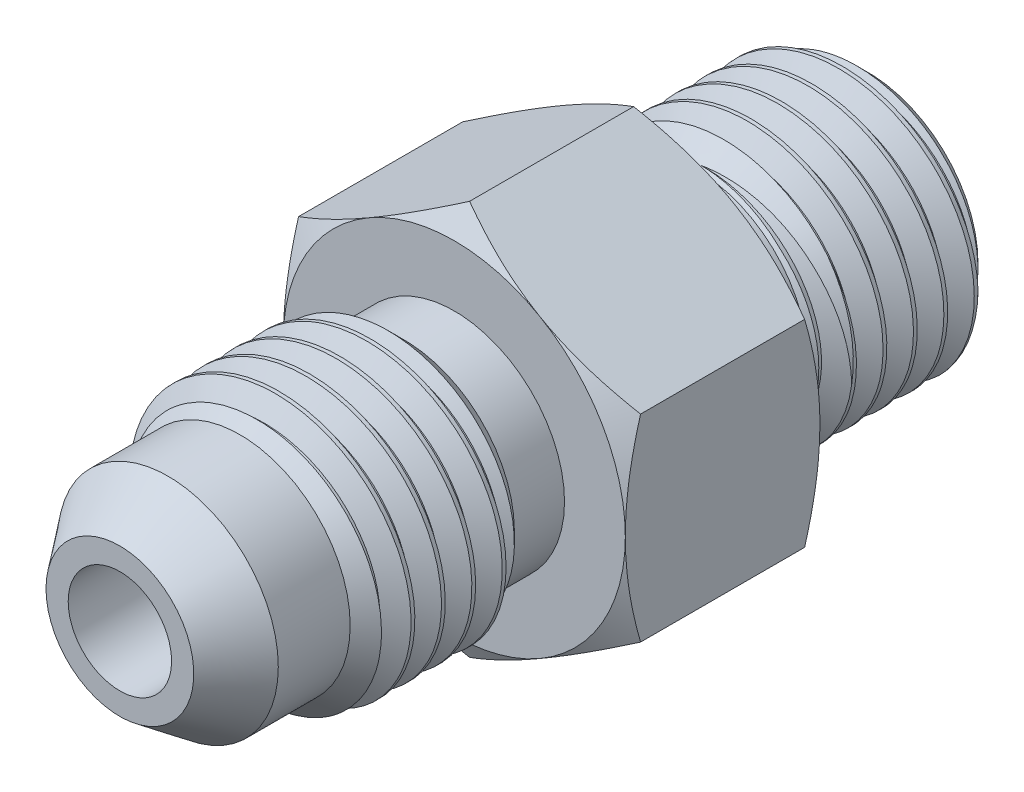
SolidWorks part; units mm, degrees
other "O-Ring" parameters "D8"=0.9525, "D1"=15.3309, "Thread Length 2"=7.112, "D2"=35.3119, "Thread Diameter 2"=6.35, "Minimum ID 2"=7.62, "Thread Pitch 2"=1.27, "Side Length 2"=9.144, "Length"=31.3538, "Side Length 1"=13.97, "Thread Length 1"=6.858, "Thread Diameter 1"=5.5562, "D3"=1.5238, "Thread 1 Offset"=0.9525, "Thread 2 Offset"=0.9525, "Thread Pitch 1"=1.27, "D4"=12.8, "Side Length Offset"=11.8745, "D5"=5.0165, "D6"=11.1125, "D7"=0.9525, "Side Length 1 Offset"=11.8745, "Face Diameter 1"=6.1722
ref_plane "Front Plane" through (0, 0, 0) normal (0, 0, 1) x (1, 0, 0)
ref_plane "Top Plane" through (0, 0, 0) normal (0, 1, 0) x (1, 0, 0)
ref_plane "Right Plane" through (0, 0, 0) normal (1, 0, 0) x (0, 0, -1)
sketch "Sketch1" plane through (0, 0, 0) normal (0, 0, 1) x (1, 0, 0)
  line L0 (0, -24.1967) -> (0, 24.1967) construction
  line L1 (0, 8.2489) -> (-7.1437, 4.1244) construction
  line L2 (-7.1437, 4.1244) -> (-7.1438, -4.1244) construction
  line L3 (-7.1438, -4.1244) -> (0, -8.2489) construction
  line L4 (0, -8.2489) -> (7.1438, -4.1244) construction
  line L5 (7.1438, -4.1244) -> (7.1438, 4.1244) construction
  line L6 (7.1438, 4.1244) -> (0, 8.2489) construction
  circle A0 centre (0, 0) radius 7.1438 construction
  circle A1 centre (0, 0) radius 2.159 construction
  point P1 (-2.159, 0)
  point P10 (-7.1437, 4.1244)
  point P11 (7.1438, 4.1244)
  point P13 (2.159, 0)
  point P14 (0, 2.159)
  point P15 (0, -2.159)
  point P16 (0, -7.1438)
  point P19 (-7.1438, -4.1244)
  point P20 (0, 8.2489)
  point P21 (0, -8.2489)
  point P22 (7.1438, -4.1244)
  point P23 (0, 7.1438)
  point P24 (7.1437, 0)
  point P25 (-7.1438, 0)
  dimension "Hex" = 14.2875
  dimension "Minimum ID 1" = 4.318
sketch "Sketch2" plane through (0, 0, 0) normal (1, 0, 0) x (0, 0, -1)
  line L0 (15.621, 0) -> (-15.621, 0) construction
  line L1 (8.509, 4.6037) -> (9.4615, 5.5562) construction
  line L2 (20.955, 0) -> (-20.955, 0) construction
  line L11 (-1.651, 7.1438) -> (6.477, 7.1438) construction
  line L12 (6.477, 7.1438) -> (6.477, 4.6037) construction
  line L13 (6.477, 4.6037) -> (8.509, 4.6037) construction
  line L21 (-15.621, 2.159) -> (-15.621, 4.6037) construction
  line L22 (8.509, 4.6037) -> (8.509, 5.5562) construction
  line L23 (8.509, 5.5562) -> (15.621, 5.5562) construction
  line L24 (15.621, 4.6037) -> (14.6685, 5.5562) construction
  line L25 (15.621, 5.5562) -> (15.621, 2.159) construction
  line L27 (-10.6045, 4.6037) -> (-10.6045, 5.5562) construction
  line L28 (-10.6045, 5.5562) -> (-3.7465, 5.5562) construction
  line L29 (-3.7465, 5.5562) -> (-3.7465, 4.6037) construction
  line L30 (-3.7465, 4.6037) -> (-1.651, 4.6037) construction
  line L31 (-1.651, 4.6037) -> (-1.651, 7.1438) construction
  line L32 (-10.6045, -5.5562) -> (-3.7465, -5.5562) construction
  line L33 (15.621, -5.5563) -> (8.509, -5.5562) construction
  line L34 (15.5416, 5.6937) -> (16.8116, 5.6937) construction
  line L35 (16.8116, 5.6937) -> (16.1766, 4.5939) construction
  line L36 (16.1766, 4.5939) -> (15.5416, 5.6937) construction
  line L37 (15.5813, 5.625) -> (16.7719, 5.625) construction
  line L38 (15.621, 5.5562) -> (16.7322, 5.5562) construction
  line L39 (16.0972, 4.7314) -> (16.256, 4.7314) construction
  line L40 (16.1766, 4.7314) -> (16.1766, 4.5939) construction
  line L41 (16.1766, 5.6937) -> (16.1766, 5.5562) construction
  line L42 (-11.7951, 5.6937) -> (-10.5251, 5.6937) construction
  line L43 (-10.5251, 5.6937) -> (-11.1601, 4.5939) construction
  line L44 (-11.1601, 4.5939) -> (-11.7951, 5.6937) construction
  line L45 (-11.7554, 5.625) -> (-10.5648, 5.625) construction
  line L46 (-11.7158, 5.5562) -> (-10.6045, 5.5562) construction
  line L47 (-11.2395, 4.7314) -> (-11.0808, 4.7314) construction
  line L48 (-11.1601, 4.7314) -> (-11.1601, 4.5939) construction
  line L49 (-11.1601, 5.5562) -> (-11.1601, 5.6937) construction
  line L53 (-15.621, 3.0861) -> (-13.607, 4.6037) construction
  line L54 (-1.651, 4.6037) -> (2.413, 4.6037) construction
  line L55 (6.477, 4.6037) -> (2.413, 4.6037) construction
  line L58 (-15.621, 2.159) -> (-1.651, 2.159) construction
  line L59 (-1.651, 2.159) -> (6.477, 2.159) construction
  line L60 (6.477, 2.159) -> (15.621, 2.159) construction
  line L61 (2.413, 2.159) -> (2.413, 7.1438) construction
  line L63 (-10.6045, 4.6037) -> (-9.652, 5.5562) construction
  line L64 (-15.621, 4.6037) -> (-10.6045, 4.6037) construction
  line L65 (-3.7465, 4.6037) -> (-4.699, 5.5562) construction
  circle A0 centre (6.9532, 5.08) radius 0.4763 construction
  point P4 (0, 0)
  point P10 (15.621, 4.6037)
  point P11 (-15.621, 2.159)
  point P16 (-10.6045, 5.5562)
  point P21 (-15.621, 4.6037)
  point P22 (-3.7465, 5.5562)
  point P24 (15.621, -5.5563)
  point P25 (-10.6045, 5.5562)
  point P26 (8.509, 4.6037)
  point P28 (15.621, 0)
  point P29 (13.716, -5.5563)
  point P31 (-1.651, 7.1438)
  point P34 (15.621, 5.5562)
  point P35 (-15.621, 0)
  point P38 (15.621, 2.159)
  point P52 (16.1766, 5.625)
  point P53 (16.256, 4.7314)
  point P54 (16.7322, 5.5562)
  point P55 (16.0972, 4.7314)
  point P56 (16.8116, 5.6937)
  point P57 (15.621, 5.5562)
  point P58 (15.5416, 5.6937)
  point P59 (-8.6995, -5.5562)
  point P66 (6.477, 7.1438)
  point P71 (-11.7158, 5.5562)
  point P72 (-11.7951, 5.6937)
  point P73 (-10.6045, 5.5562)
  point P74 (-10.5251, 5.6937)
  point P75 (-11.2395, 4.7314)
  point P76 (-11.0808, 4.7314)
  point P79 (-11.1601, 5.625)
  point P82 (-15.621, 3.0861)
  point P83 (-10.6045, -5.5562)
  point P84 (-13.607, 4.6037)
  dimension "D2" = 0.1588
  dimension "Length" = 31.242
  dimension "D1" = 1.905
  dimension "Thread 2 Offset" = 0.9525
  dimension "D3" = 0.1588
  dimension "D4" = 1.905
  dimension "Thread Diameter 1" = 11.1125
  dimension "Thread Diameter 2" = 11.1125
  dimension "D6" = 45
  dimension "D7" = 45
  dimension "Minimum ID 2" = 4.318
  dimension "D5" = 37
ref_plane "Plane1" through (0, 0, 10.6045) normal (0, 0, 1) x (1, 0, 0)
ref_plane "Plane2" through (0, 0, -15.621) normal (0, 0, 1) x (1, 0, 0)
ref_plane "Plane3" through (0, 0, 1.651) normal (0, 0, 1) x (1, 0, 0)
sketch "Sketch3" plane through (0, 0, 0) normal (1, 0, 0) x (0, 0, -1)
  line L0 (15.621, 0) -> (-15.621, 0) construction
  line L1 (-15.621, 2.159) -> (-15.621, 4.6037) construction
  line L2 (-15.621, 2.159) -> (-1.651, 2.159) construction
  line L3 (-1.651, 2.159) -> (6.477, 2.159) construction
  line L4 (6.477, 2.159) -> (15.621, 2.159) construction
  line L5 (15.621, 5.5562) -> (15.621, 2.159) construction
  line L6 (15.621, 4.6037) -> (14.6685, 5.5562) construction
  line L7 (8.509, 5.5562) -> (15.621, 5.5562) construction
  line L8 (8.509, 4.6037) -> (9.4615, 5.5562) construction
  line L10 (-3.7465, 4.6037) -> (-1.651, 4.6037)
  line L12 (-15.621, 4.6037) -> (-10.6045, 4.6037) construction
  line L14 (8.509, 4.6037) -> (6.477, 4.6037)
  line L15 (-10.6045, 5.5562) -> (-3.7465, 5.5562) construction
  line L16 (-10.6045, 4.6037) -> (-9.652, 5.5562) construction
  line L17 (-15.621, 3.0861) -> (-13.607, 4.6037) construction
  line L18 (-15.621, 3.0861) -> (-13.607, 4.6037)
  line L19 (15.621, 0) -> (-15.621, 0) construction
  line L20 (-15.621, 2.159) -> (-15.621, 3.0861)
  line L21 (-15.621, 2.159) -> (-1.651, 2.159)
  line L22 (-1.651, 2.159) -> (6.477, 2.159)
  line L23 (6.477, 2.159) -> (15.621, 2.159)
  line L24 (15.621, 4.6037) -> (15.621, 2.159)
  line L25 (15.621, 4.6037) -> (14.6685, 5.5562)
  line L26 (9.4615, 5.5562) -> (14.6685, 5.5562)
  line L27 (8.509, 4.6037) -> (9.4615, 5.5562)
  line L34 (-9.652, 5.5562) -> (-4.699, 5.5562)
  line L35 (-10.6045, 4.6037) -> (-9.652, 5.5562)
  line L36 (-13.607, 4.6037) -> (-10.6045, 4.6037)
  line L37 (-3.7465, 4.6037) -> (-4.699, 5.5562) construction
  line L41 (-1.651, 4.6037) -> (6.477, 4.6037)
  line L46 (-3.7465, 4.6037) -> (-4.699, 5.5562)
revolve "Revolve1" add sketch "Sketch3" angle 360 about L19
sketch "Sketch4" plane through (0, 0, 1.651) normal (0, 0, 1) x (1, 0, 0)
  line L0 (-7.1437, 4.1244) -> (-7.1438, -4.1244) construction
  line L1 (-7.1438, -4.1244) -> (0, -8.2489) construction
  line L2 (0, -8.2489) -> (7.1438, -4.1244) construction
  line L3 (7.1438, -4.1244) -> (7.1438, 4.1244) construction
  line L4 (7.1438, 4.1244) -> (0, 8.2489) construction
  line L5 (0, 8.2489) -> (-7.1437, 4.1244) construction
  line L6 (-7.1437, 4.1244) -> (-7.1438, -4.1244)
  line L7 (-7.1438, -4.1244) -> (0, -8.2489)
  line L8 (0, -8.2489) -> (7.1438, -4.1244)
  line L9 (7.1438, -4.1244) -> (7.1438, 4.1244)
  line L10 (7.1438, 4.1244) -> (0, 8.2489)
  line L11 (0, 8.2489) -> (-7.1437, 4.1244)
extrude "Boss-Extrude1" add sketch "Sketch4" against normal up to vertex (8.128 mm away) up to point (0, 7.1438, -6.477)
sketch "Sketch5" plane through (0, 0, 0) normal (1, 0, 0) x (0, 0, -1)
  line L0 (15.621, 0) -> (-15.621, 0) construction
  line L1 (6.477, 2.159) -> (15.621, 2.159) construction
  line L2 (-1.651, 2.159) -> (6.477, 2.159) construction
  line L3 (-15.621, 2.159) -> (-1.651, 2.159) construction
  line L4 (15.621, 0) -> (-15.621, 0)
  line L5 (6.477, 2.159) -> (15.621, 2.159)
  line L6 (-1.651, 2.159) -> (6.477, 2.159)
  line L7 (-15.621, 2.159) -> (-1.651, 2.159)
  line L8 (-15.621, 2.159) -> (-15.621, 0)
  line L9 (15.621, 2.159) -> (15.621, 0)
revolve "Cut-Revolve1" cut sketch "Sketch5" angle 360 about L4
sketch "Sketch6" plane through (0, 0, 1.651) normal (0, 0, 1) x (1, 0, 0)
  circle A0 centre (0, 0) radius 7.1438 construction
  circle A1 centre (0, 0) radius 7.1438
extrude "Cut-Extrude1" cut sketch "Sketch6" against normal through all draft 60 flip side to cut
sketch "Sketch7" plane through (0, 0, -6.477) normal (0, 0, -1) x (-1, 0, 0)
  circle A0 centre (0, 0) radius 7.1438 construction
  circle A1 centre (0, 0) radius 7.1438
extrude "Cut-Extrude2" cut sketch "Sketch7" against normal through all draft 60 flip side to cut
sketch "Sketch8" plane through (0, 0, 0) normal (1, 0, 0) x (0, 0, -1)
  circle A0 centre (6.9532, 5.08) radius 0.4763 construction
  circle A1 centre (6.9532, 5.08) radius 0.4763
revolve "Revolve2" add sketch "Sketch8" angle 360 about L0
sketch "Sketch9" plane through (0, 0, 10.6045) normal (0, 0, 1) x (1, 0, 0)
  circle A4 centre (0, 0) radius 5.5562
curve "Helix/Spiral1" pitch 1.27 height 8.128 turns 6.4
sketch "Sketch10" plane through (0, 0, 0) normal (1, 0, 0) x (0, 0, -1)
  line L0 (-11.2395, 4.7314) -> (-11.0808, 4.7314) construction
  line L1 (-11.7554, 5.625) -> (-10.5648, 5.625) construction
  line L2 (-11.2395, 4.7314) -> (-11.0808, 4.7314)
  line L3 (-11.7554, 5.625) -> (-10.5648, 5.625)
  line L4 (-10.5251, 5.6937) -> (-11.1601, 4.5939) construction
  line L5 (-11.1601, 4.5939) -> (-11.7951, 5.6937) construction
  line L6 (-10.5648, 5.625) -> (-11.0808, 4.7314)
  line L7 (-11.2395, 4.7314) -> (-11.7554, 5.625)
sweep "Cut-Sweep1" cut profiles "Sketch10" path "Helix/Spiral1"
sketch "Sketch11" plane through (0, 0, -15.621) normal (0, 0, 1) x (1, 0, 0)
  circle A0 centre (0, 0) radius 5.5562
curve "Helix/Spiral2" pitch 1.27 height 8.382 turns 6.6
sketch "Sketch12" plane through (0, 0, 0) normal (1, 0, 0) x (0, 0, -1)
  line L0 (16.1766, 4.5939) -> (15.5416, 5.6937) construction
  line L1 (16.8116, 5.6937) -> (16.1766, 4.5939) construction
  line L2 (16.0972, 4.7314) -> (16.256, 4.7314) construction
  line L3 (15.5813, 5.625) -> (16.7719, 5.625) construction
  line L4 (16.0972, 4.7314) -> (15.5813, 5.625)
  line L5 (16.7719, 5.625) -> (16.256, 4.7314)
  line L6 (16.0972, 4.7314) -> (16.256, 4.7314)
  line L7 (15.5813, 5.625) -> (16.7719, 5.625)
sweep "Cut-Sweep2" cut profiles "Sketch12" path "Helix/Spiral2"
sketch "Sketch13" plane through (0, 0, -6.477) normal (0, 0, -1) x (-1, 0, 0)
  circle A0 centre (0, 0) radius 7.1438 construction
  circle A1 centre (0, 0) radius 7.1438
  circle A2 centre (0, 0) radius 2.159
  point P3 (0, 2.159)
extrude "Boss-Extrude2" add sketch "Sketch13" against normal up to vertex (8.128 mm away) up to point (0, 7.1438, 1.651)
equation "\"D2@Sketch2\"=\"Thread Pitch 2@Sketch2\"/8"
equation "\"D1@Sketch2\"=\"Thread Pitch 2@Sketch2\"*1.5"
equation "\"D3@Sketch2\"=\"Thread Pitch 1@Sketch2\"/8"
equation "\"D4@Sketch2\"=\"Thread Pitch 1@Sketch2\"*1.5"
equation "\"D3@Helix/Spiral1\"=\"Thread Length 1@Sketch2\"+\"Thread Pitch 1@Sketch2\""
equation "\"D4@Helix/Spiral1\"=\"Thread Pitch 1@Sketch2\""
equation "\"D3@Helix/Spiral2\"=\"Thread Length 2@Sketch2\"+\"Thread Pitch 2@Sketch2\""
equation "\"D4@Helix/Spiral2\"=\"Thread Pitch 2@Sketch2\""
